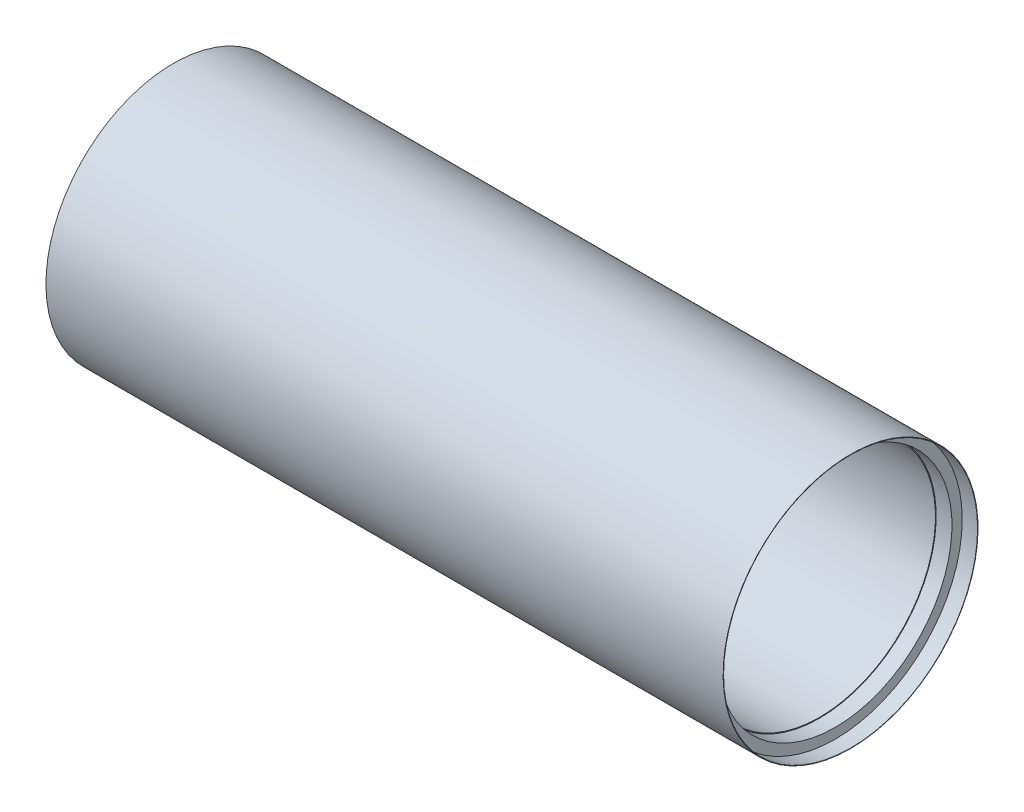
SolidWorks part; units mm, degrees
material "Hexcel AS4C (3000 Filaments)"
ref_plane "Front" through (0, 0, 0) normal (0, 0, 1) x (1, 0, 0)
ref_plane "Top" through (0, 0, 0) normal (0, 1, 0) x (1, 0, 0)
ref_plane "Right" through (0, 0, 0) normal (1, 0, 0) x (0, 0, -1)
sketch "Sketch1" plane through (0, 0, 0) normal (0, 0, 1) x (1, 0, 0)
  line L0 (0, 83.9724) -> (10.16, 83.9724)
  line L1 (10.16, 83.9724) -> (10.16, 77.2414)
  line L2 (20.574, 76.7334) -> (427.5582, 76.7334)
  line L3 (437.9722, 77.2414) -> (437.9722, 84.0486)
  line L4 (437.9722, 84.0486) -> (448.1322, 84.0486)
  line L5 (448.1322, 84.0486) -> (448.1322, 84.3534)
  line L6 (448.1322, 84.3534) -> (0, 84.3534)
  line L7 (0, 84.3534) -> (0, 83.9724)
  line L8 (0, 0) -> (134.0356, 0) construction
  line L9 (10.16, 77.2414) -> (20.574, 77.2414)
  line L10 (20.574, 77.2414) -> (20.574, 76.7334)
  line L11 (437.9722, 77.2414) -> (427.5582, 77.2414)
  line L12 (427.5582, 77.2414) -> (427.5582, 76.7334)
  line L13 (0, 0) -> (0, 83.9724) construction
  dimension "D1" = 76.7334
  dimension "D2" = 0.381
  dimension "D3" = 10.16
  dimension "D4" = 10.16
  dimension "D5" = 427.8122
  dimension "D6" = 84.3534
  dimension "D7" = 0.3048
  dimension "D8" = 10.414
  dimension "D9" = 10.414
  dimension "D10" = 0.508
  dimension "D11" = 0.508
revolve "Revolve1" add sketch "Sketch1" angle 360 about L8 region at (224.014, 80.5627, 0)
ref_axis "Axis1" through (427.5582, 0, 0) along (-1, 0, 0)
